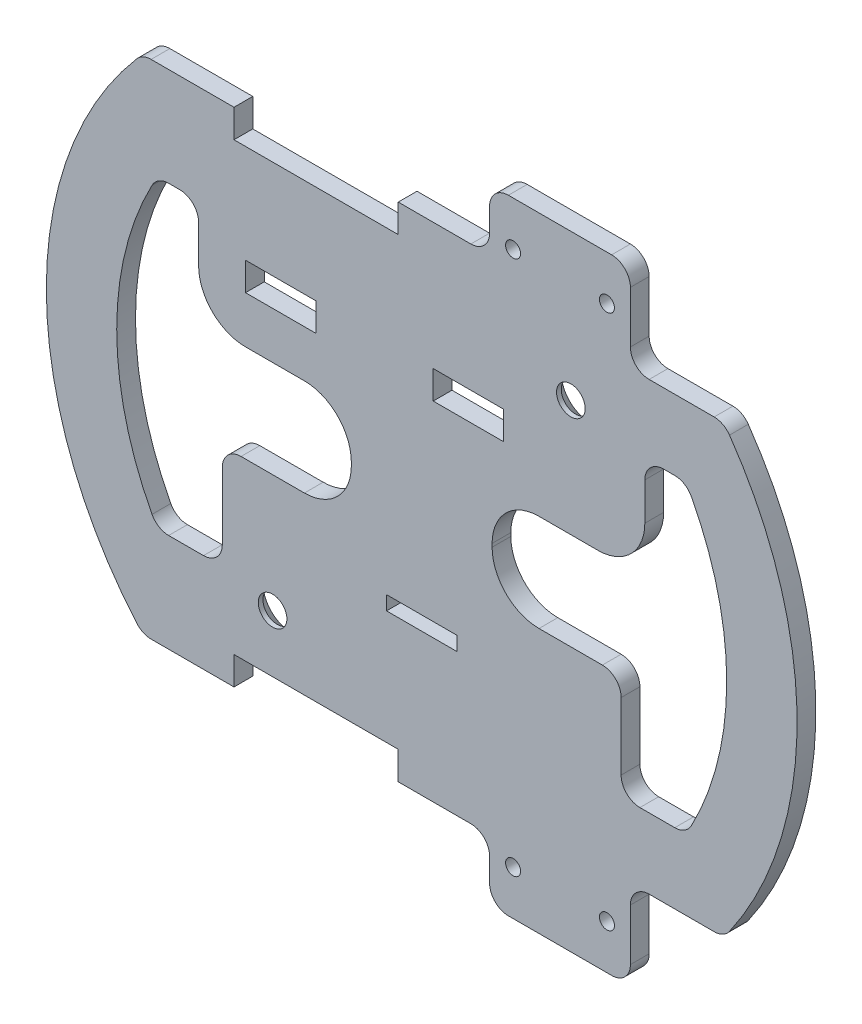
SolidWorks part; units mm, degrees
material "Acrílico (médio-alto impacto)"
ref_plane "Plano frontal" through (0, 0, 0) normal (0, 0, 1) x (1, 0, 0)
ref_plane "Plano superior" through (0, 0, 0) normal (0, 1, 0) x (1, 0, 0)
ref_plane "Plano direito" through (0, 0, 0) normal (1, 0, 0) x (0, 0, -1)
sketch "Esboço1" plane through (0, 0, 0) normal (0, 0, 1) x (1, 0, 0)
  line L0 (80, 0) -> (0, 0) construction
  line L1 (-80, -66.5) -> (80, -66.5)
  line L2 (-80, -66.5) -> (-80, 66.5)
  line L3 (-80, 66.5) -> (80, 66.5)
  line L4 (80, -66.5) -> (80, 66.5)
  line L5 (-80, -66.5) -> (80, 66.5) construction
  line L6 (-80, 66.5) -> (80, -66.5) construction
  line L7 (80, 47.5) -> (-80, 47.5) construction
  line L8 (80, -47.5) -> (-80, -47.5) construction
  line L9 (14.4719, 66.5) -> (14.4719, 53.5)
  line L10 (0, 0) -> (0, 66.5) construction
  line L11 (44.4719, 47.5) -> (44.4719, 66.5)
  line L12 (44.4719, -47.5) -> (44.4719, -66.5)
  line L13 (14.4719, -66.5) -> (14.4719, -53.5)
  line L14 (14.4719, 53.5) -> (-59.479, 53.5)
  line L15 (14.4719, -53.5) -> (-59.479, -53.5)
  line L16 (-5.0035, 47.5) -> (-40.0035, 47.5)
  line L17 (-5.0035, 47.5) -> (-5.0035, 53.5)
  line L18 (-31.7837, -35.2994) -> (31.7837, 35.2994) construction
  line L19 (-42.5, -20.2) -> (-42.5, -14.2) construction
  line L20 (-7.5, -20.2) -> (7.5, -20.2)
  line L21 (-7.5, -20.2) -> (-7.5, -23.2)
  line L22 (-7.5, -23.2) -> (7.5, -23.2)
  line L23 (7.5, -20.2) -> (7.5, -23.2)
  line L24 (-7.5, -20.2) -> (7.5, -23.2) construction
  line L25 (-7.5, -23.2) -> (7.5, -20.2) construction
  line L26 (-37.55, 26.5) -> (-22.55, 26.5)
  line L27 (-37.55, 26.5) -> (-37.55, 20.5)
  line L28 (-37.55, 20.5) -> (-22.55, 20.5)
  line L29 (-22.55, 26.5) -> (-22.55, 20.5)
  line L30 (-37.55, 26.5) -> (-22.55, 20.5) construction
  line L31 (-37.55, 20.5) -> (-22.55, 26.5) construction
  line L32 (17.45, 20.5) -> (2.45, 20.5)
  line L33 (17.45, 20.5) -> (17.45, 26.5)
  line L34 (17.45, 26.5) -> (2.45, 26.5)
  line L35 (2.45, 20.5) -> (2.45, 26.5)
  line L36 (17.45, 20.5) -> (2.45, 26.5) construction
  line L37 (17.45, 26.5) -> (2.45, 20.5) construction
  line L38 (-42.5, -14.2) -> (42.5, -14.2) construction
  line L39 (42.5, -14.2) -> (42.5, -20.2) construction
  line L40 (42.5, -20.2) -> (-42.5, -20.2) construction
  line L41 (-56.2917, 32.5) -> (-47.55, 32.5)
  line L42 (-47.55, 32.5) -> (-47.55, 10.5)
  line L43 (-47.55, 10.5) -> (-15, 10.5)
  line L44 (-15, 10.5) -> (-15, -10.2)
  line L47 (-42.5, -32.5) -> (-56.2917, -32.5)
  line L48 (-42.5, -32.5) -> (-42.5, -10.2)
  line L49 (-42.5, -10.2) -> (-15, -10.2)
  line L50 (15, -10.2) -> (15, 10.5)
  line L51 (15, 10.5) -> (47.55, 10.5)
  line L52 (47.55, 10.5) -> (47.55, 32.5)
  line L53 (47.55, 32.5) -> (56.2917, 32.5)
  line L54 (56.2917, -32.5) -> (42.5, -32.5)
  line L55 (15, -10.2) -> (42.5, -10.2)
  line L56 (42.5, -10.2) -> (42.5, -32.5)
  line L57 (15, 10.5) -> (-15, 10.5) construction
  line L58 (-21.0674, -35.2994) -> (-42.5, -35.2994) construction
  line L59 (-5.0035, 53.5) -> (-40.0035, 53.5)
  line L60 (-40.0035, 47.5) -> (-40.0035, 53.5)
  line L61 (-5.0035, 47.5) -> (-40.0035, 53.5) construction
  line L62 (-5.0035, 53.5) -> (-40.0035, 47.5) construction
  line L63 (-5.0035, -53.5) -> (-40.0035, -53.5)
  line L64 (-40.0035, -47.5) -> (-40.0035, -53.5)
  line L65 (-5.0035, -47.5) -> (-40.0035, -47.5)
  line L66 (-5.0035, -47.5) -> (-5.0035, -53.5)
  line L67 (24.9009, 47.5) -> (24.9009, 66.5) construction
  line L69 (44.4719, 47.5) -> (64.372, 47.5)
  line L70 (44.4719, -47.5) -> (64.372, -47.5)
  circle A0 centre (0, 0) radius 80
  circle A1 centre (-31.7837, -35.2994) radius 3.05
  circle A2 centre (31.7837, 35.2994) radius 3.05
  circle A3 centre (19.4719, 57) radius 1.6
  circle A8 centre (19.4719, -57) radius 1.6
  arc A9 (-56.2917, -32.5) -> (-56.2917, 32.5) centre (0, 0) cw
  arc A10 (56.2917, -32.5) -> (56.2917, 32.5) centre (0, 0) ccw
  circle A11 centre (39.4719, 57) radius 1.6
  circle A12 centre (39.4719, -57) radius 1.6
  point P0 (0, 0)
  point P17 (-22.5035, 50.5)
  point P22 (44.4719, 66.5)
  point P34 (-30.05, 23.5)
  point P44 (0, -21.7)
  point P53 (9.95, 23.5)
  point P58 (0, -20.2)
  point P65 (-65, 0)
  point P80 (0, 10.5)
  point P83 (24.9009, 57)
  point P84 (-22.5035, 53.5)
  dimension "D6" = 6.1
  dimension "D7" = 6
  dimension "D18" = 15
  dimension "D25" = 3.2
  dimension "D1" = 95
  dimension "D2" = 19
  dimension "D3" = 160
  dimension "D4" = 95
  dimension "D5" = 48
  dimension "D8" = 5
  dimension "D9" = 3
  dimension "D10" = 6
  dimension "D11" = 15
  dimension "D12" = 20.2
  dimension "D13" = 40.7
  dimension "D14" = 25
  dimension "D15" = 2.45
  dimension "D16" = 85
  dimension "D17" = 35
  dimension "D19" = 10
  dimension "D20" = 10
  dimension "D21" = 10
  dimension "D22" = 30
  dimension "D23" = 30
  dimension "D24" = 5
  dimension "D26" = 15
extrude "Ressalto-extrusão1" add sketch "Esboço1" along normal blind 4 contours A0 L13 L1 L3 L9 A10 L54 L56 L55 L50 L51 L52 L53 L32 L35 L34 L33 L26 L29 L28 L27 L20 L23 L22 L21 A1 A2 A3 A11 region at (1.8253, 0.1118, 0)
chamfer "Chanfro1" distance 3 angle 45 2 edges at (34.8337, 35.2994, 0) (-28.7337, -35.2994, 0)
fillet "Filete1" radius 4 22 edges at (56.2917, 32.5, 2) (47.55, 32.5, 2) (42.5, -32.5, 2) (56.2917, -32.5, 2) (-42.5, -32.5, 2) (-56.2917, -32.5, 2) (42.5, -10.2, 2) (-42.5, -10.2, 2) (-47.55, 32.5, 2) (-56.2917, 32.5, 2) (14.4719, -53.5, 2) (14.4719, 53.5, 2) (44.4719, 47.5, 2) (44.4719, -47.5, 2) (14.4719, 66.5, 2) (44.4719, 66.5, 2) (44.4719, -66.5, 2) (14.4719, -66.5, 2) (-59.479, 53.5, 2) (64.372, 47.5, 2) (64.372, -47.5, 2) (-59.479, -53.5, 2)
fillet "Filete2" radius 10 6 edges at (15, -10.2, 2) (-15, -10.2, 2) (-15, 10.5, 2) (15, 10.5, 2) (47.55, 10.5, 2) (-47.55, 10.5, 2)
